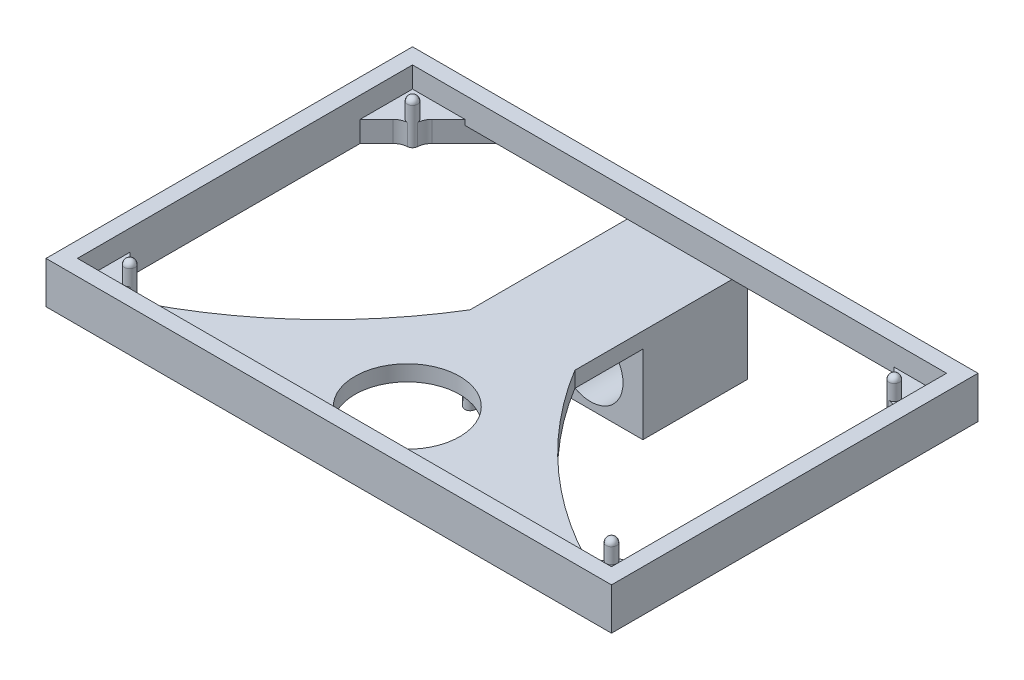
SolidWorks part; units mm, degrees
ref_plane "前视基准面" through (0, 0, 0) normal (0, 0, 1) x (1, 0, 0)
ref_plane "上视基准面" through (0, 0, 0) normal (0, 1, 0) x (1, 0, 0)
ref_plane "右视基准面" through (0, 0, 0) normal (1, 0, 0) x (0, 0, -1)
sketch "草图1" plane through (0, 0, 0) normal (0, 1, 0) x (1, 0, 0)
  line L0 (-54, -35) -> (-54, 35)
  line L1 (-51, -32) -> (51, -32)
  line L2 (-51, -32) -> (-51, 32)
  line L3 (-51, 32) -> (51, 32)
  line L4 (51, -32) -> (51, 32)
  line L5 (-51, -32) -> (51, 32) construction
  line L6 (-51, 32) -> (51, -32) construction
  line L7 (-54, 35) -> (54, 35)
  line L8 (54, -35) -> (54, 35)
  line L9 (-54, -35) -> (54, -35)
  point P0 (0, 0)
  dimension "D1" = 102
  dimension "D2" = 64
  dimension "D3" = 3
extrude "凸台-拉伸1" add sketch "草图1" along normal blind 5
sketch "草图3" plane through (0, 0, 0) normal (0, -1, 0) x (1, 0, 0)
  line L0 (0, -37.7062) -> (0, 42.9675) construction
  line L1 (10, -35) -> (-10, -35)
  line L2 (51, -32) -> (-51, -32) construction
  line L3 (10, -35) -> (10, -2)
  line L4 (54, 28.0076) -> (54, 38.9784) construction
  line L5 (54, 35) -> (54, -35) construction
  line L6 (54, 33.0651) -> (54, 35)
  line L7 (54, 35) -> (-54, 35)
  line L8 (-54, 35) -> (54, 35) construction
  line L9 (-10, -35) -> (-10, -2)
  line L10 (-54, 33.0651) -> (-54, 35)
  line L11 (54, -35) -> (-54, -35) construction
  arc A0 (54, 33.0651) -> (10, -2) centre (79.8551, -44.5165) ccw
  arc A1 (-54, 33.0651) -> (-10, -2) centre (-79.8551, -44.5165) cw
  point P21 (0, -32)
  point P25 (0, 35)
extrude "凸台-拉伸8" add sketch "草图3" along normal blind 3
sketch "草图4" plane through (0, 0, -35) normal (0, 0, -1) x (-1, 0, 0)
  line L0 (10, 0) -> (-10, 0)
  line L1 (10, 0) -> (10, -18)
  line L2 (-10, 0) -> (-10, -18)
  line L3 (10, -18) -> (-10, -18)
  dimension "D1" = 18
extrude "凸台-拉伸9" add sketch "草图4" against normal blind 20
sketch "草图5" plane through (0, 0, -15) normal (0, 0, 1) x (1, 0, 0)
  line L0 (-10, -10.5) -> (10, -10.5) construction
  line L1 (-10, -18) -> (-10, -3) construction
  line L2 (10, -3) -> (10, -18) construction
  circle A0 centre (0, -10.5) radius 6.2
  dimension "D1" = 12.4
extrude "切除-拉伸1" cut sketch "草图5" against normal through all
fillet "圆角2" radius 1 1 edges at (0, 0, 32)
sketch "草图6" plane through (0, 0, 0) normal (0, 1, 0) x (1, 0, 0)
  line L0 (51, 32) -> (41, 32)
  line L1 (51, 32) -> (10, 32) construction
  line L2 (41, 32) -> (51, 22)
  line L3 (51, -31) -> (51, 32) construction
  line L4 (51, 22) -> (51, 32)
  line L5 (0, -9.5527) -> (0, 13.1799) construction
  line L6 (-7.8165, 0) -> (11.2572, 0) construction
  line L7 (-51, 32) -> (-41, 32)
  line L8 (-51, 22) -> (-51, 32)
  line L9 (-41, 32) -> (-51, 22)
  line L10 (-51, -22) -> (-51, -32)
  line L11 (-51, -32) -> (-41, -32)
  line L12 (-41, -32) -> (-51, -22)
  line L13 (51, -32) -> (41, -32)
  line L14 (51, -22) -> (51, -32)
  line L15 (41, -32) -> (51, -22)
  arc A0 (10, 2) -> (48.476, -31) centre (79.8551, 44.5165) ccw construction
  dimension "D1" = 10
  dimension "D2" = 10
extrude "凸台-拉伸10" add sketch "草图6" along normal blind 1
sketch "草图7" plane through (0, 0, 0) normal (0, -1, 0) x (1, 0, 0)
  line L0 (38, -35) -> (54, -19)
  line L1 (54, -35) -> (10, -35) construction
  line L2 (54, 33.0651) -> (54, -35) construction
  line L3 (54, -19) -> (54, -35)
  line L4 (54, -35) -> (38, -35)
  line L5 (41, -32) -> (51, -22) construction
  line L6 (6.6655, 0) -> (-5.796, 0) construction
  line L7 (0, -7.7525) -> (0, 9.6789) construction
  line L8 (-54, -35) -> (-38, -35)
  line L9 (-54, -19) -> (-54, -35)
  line L10 (-38, -35) -> (-54, -19)
  line L11 (54, 35) -> (38, 35)
  line L12 (54, 19) -> (54, 35)
  line L13 (38, 35) -> (54, 19)
  line L14 (-54, 35) -> (-38, 35)
  line L15 (-38, 35) -> (-54, 19)
  line L16 (-54, 19) -> (-54, 35)
extrude "凸台-拉伸11" add sketch "草图7" along normal blind 3
fillet "圆角3" radius 3 2 edges at (44.0131, -1.5, 28.9869) (-44.0131, -1.5, 28.9869)
sketch "草图8" plane through (0, 0, 0) normal (0, 1, 0) x (1, 0, 0)
  circle A0 centre (0, -20) radius 10
  point P2 (0, 0)
  point P3 (0, 0)
  dimension "D2" = 20
  dimension "D1" = 20
extrude "切除-拉伸2" cut sketch "草图8" against normal mid plane 10
sketch "草图9" plane through (0, 1, 0) normal (0, 1, 0) x (1, 0, 0)
  line L0 (51, -32) -> (51, -22) construction
  line L2 (51, -32) -> (41, -32) construction
  line L3 (-1.9165, 0) -> (2.645, 0) construction
  line L4 (0, -2.5181) -> (0, 3.8535) construction
  circle A0 centre (46, -27) radius 1
  circle A1 centre (-46, -27) radius 1
  circle A2 centre (-46, 27) radius 1
  circle A3 centre (46, 27) radius 1
  dimension "D1" = 2
  dimension "D2" = 5
  dimension "D3" = 5
extrude "凸台-拉伸12" add sketch "草图9" against normal mid plane 8
fillet "圆角4" radius 3 6 edges at (46.7071, -1, 26.2929) (-46.7071, -1, 26.2929) (-46.7071, -1, -26.2929) (-45.2929, -1, -27.7071) (45.2929, -1, -27.7071) (46.7071, -1, -26.2929)
fillet "圆角5" radius 1 4 edges at (46, 5, 28) (46, 5, -28) (-46, 5, -26) (-46, 5, 26)
sketch "草图10" plane through (0, 0, 0) normal (0, -1, 0) x (1, 0, 0)
  line L0 (-51, 22) -> (-54, 19)
  line L1 (-54, 19) -> (-54, -19)
  line L2 (-54, -19) -> (-51, -22)
  line L3 (-51, -22) -> (-51, 22)
  line L4 (0, -8.3229) -> (0, 12.6564) construction
  line L5 (54, -19) -> (51, -22)
  line L6 (51, -22) -> (51, 22)
  line L7 (51, 22) -> (54, 19)
  line L8 (54, 19) -> (54, -19)
extrude "凸台-拉伸13" add sketch "草图10" along normal blind 3
sketch "草图12" plane through (0, -3, 0) normal (0, -1, 0) x (1, 0, 0)
  line L0 (0, 4.0403) -> (0, -11.7961) construction
  line L1 (-10, -15) -> (10, -15) construction
  circle A0 centre (0, -8) radius 1
  circle A1 centre (0, 8) radius 1
  dimension "D1" = 2
  dimension "D2" = 2
  dimension "D3" = 16
  dimension "D4" = 7
extrude "凸台-拉伸15" add sketch "草图12" along normal blind 3
